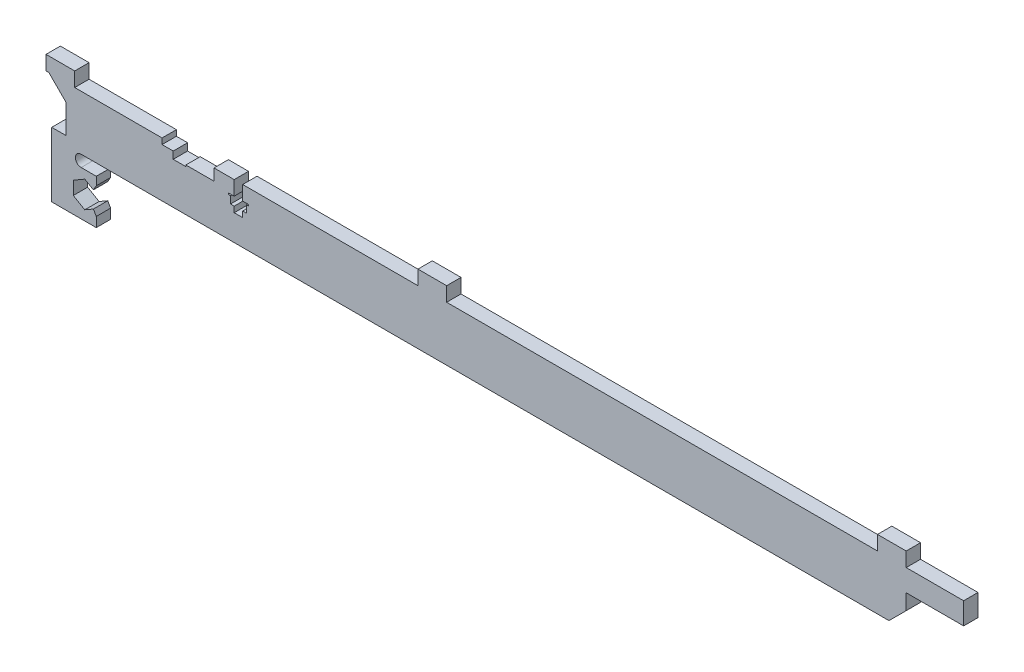
SolidWorks part; units mm, degrees
material "6061-T6 Black anodised"
ref_plane "Front Plane" through (0, 0, 0) normal (0, 0, 1) x (1, 0, 0)
ref_plane "Top Plane" through (0, 0, 0) normal (0, 1, 0) x (1, 0, 0)
ref_plane "Right Plane" through (0, 0, 0) normal (1, 0, 0) x (0, 0, -1)
sketch "Sketch1" plane through (0, 0, 0) normal (0, 0, 1) x (1, 0, 0)
  line L0 (-250.8, 3.6) -> (-241, 3.6)
  line L1 (0, 0) -> (20, 0)
  line L2 (-232.5, 8.6) -> (-232.5, -2.4) construction
  line L3 (0, 7.6) -> (20, 7.6)
  line L4 (20, 0) -> (20, 7.6)
  line L5 (-10, 7.6) -> (-160, 7.6)
  line L6 (0, 0) -> (0, -11.4)
  line L7 (0, -11.4) -> (-287.2708, -11.4)
  line L8 (-292.5, 1.6) -> (-292.5, -8.4)
  line L9 (-259.0932, 7.6) -> (-289.5, 7.6)
  line L10 (-299.5, 7.6) -> (-299.5, 12.6)
  line L11 (-299.5, 12.6) -> (-289.5, 12.6)
  line L12 (-289.5, 7.6) -> (-289.5, 12.6)
  line L13 (-170, 7.6) -> (-170, 12.6)
  line L14 (-250.8, 3.6) -> (-250.8, 3.1)
  line L15 (-250.8, 3.1) -> (-255.2, 3.1)
  line L16 (-255.2, 3.1) -> (-255.2, 5.6)
  line L17 (-255.2, 5.6) -> (-259.0932, 5.6)
  line L18 (0, 7.6) -> (0, 12.6)
  line L19 (0, 12.6) -> (-10, 12.6)
  line L20 (-10, 7.6) -> (-10, 12.6)
  line L21 (-259.0932, 5.6) -> (-259.0932, 7.6)
  line L22 (-255, 3.6) -> (-251, 3.6) construction
  line L23 (-255, 3.6) -> (-255, 13.6) construction
  line L24 (-251, 3.6) -> (-251, 13.6) construction
  line L25 (-255, 13.6) -> (-251, 13.6) construction
  line L26 (-255, 3.6) -> (-251, 13.6) construction
  line L27 (-271, 32.6) -> (-219.2068, 32.6) construction
  line L28 (-271, 32.6) -> (-271, 13.6) construction
  line L29 (-250, 33.6) -> (-250, 13.6) construction
  line L30 (-271, 13.6) -> (-250, 13.6) construction
  line L31 (-271, 32.6) -> (-250, 13.6) construction
  line L32 (-250, 33.6) -> (-271, 13.6) construction
  line L33 (-170, 12.6) -> (-160, 12.6)
  line L34 (-160, 12.6) -> (-160, 7.6)
  line L35 (-170, 7.6) -> (-231.02, 7.6)
  line L36 (-299.5, 7.6) -> (-298.5, 7.6)
  line L37 (-298.5, 7.6) -> (-292.5, 1.6)
  line L38 (-233.98, 7.6) -> (-233.98, 2.6)
  line L39 (-233.98, 2.6) -> (-236, 2.6)
  line L40 (-236, 2.6) -> (-236, 2.1)
  line L41 (-236, 2.1) -> (-235.25, 2.1)
  line L42 (-235.25, 2.1) -> (-235.25, -0.4)
  line L43 (-235.25, -0.4) -> (-233.98, -0.4)
  line L44 (-233.98, -0.4) -> (-233.98, -2.4)
  line L45 (-233.98, -2.4) -> (-231.02, -2.4)
  line L46 (-233.98, 7.6) -> (-241, 7.6)
  line L47 (-231.02, -0.4) -> (-231.02, -2.4)
  line L48 (-229.75, -0.4) -> (-231.02, -0.4)
  line L49 (-229.75, 2.1) -> (-229.75, -0.4)
  line L50 (-229, 2.1) -> (-229.75, 2.1)
  line L51 (-229, 2.6) -> (-229, 2.1)
  line L52 (-231.02, 2.6) -> (-229, 2.6)
  line L53 (-231.02, 7.6) -> (-231.02, 2.6)
  line L54 (-283, -20.0132) -> (-282, -18.2812)
  line L56 (-282, -15.4) -> (-287.2708, -15.4)
  line L57 (-251, 3.6) -> (-255, 13.6) construction
  line L58 (-282, -15.4) -> (-282, -18.2812)
  line L60 (-282, -30.9) -> (-297.5, -30.9)
  line L61 (-297.5, -30.9) -> (-297.5, -8.4)
  line L62 (-297.5, -8.4) -> (-292.5, -8.4)
  line L63 (-283, -25.7868) -> (-282, -27.5188)
  line L64 (-282, -23.9) -> (-282, -20.3633) construction
  line L65 (-283, -20.0132) -> (-286, -18.2812)
  line L66 (-286, -18.2812) -> (-290, -20.5906)
  line L67 (-290, -20.5906) -> (-290, -25.2094)
  line L68 (-290, -25.2094) -> (-286, -27.5188)
  line L69 (-286, -27.5188) -> (-283, -25.7868)
  line L70 (-282, -27.5188) -> (-282, -30.9)
  line L100 (-253, 8.6) -> (-238.8671, 8.6) construction
  line L116 (-241, 7.6) -> (-241, 3.6)
  arc A0 (-287.2708, -11.4) -> (-287.2708, -15.4) centre (-287.2708, -13.4) ccw
  circle A1 centre (-286, -22.9) radius 4 construction
  point P27 (-253, 8.6)
  point P130 (-242, 8.6)
  dimension "D21" = 0.5
  dimension "D24" = 0.5
  dimension "D26" = 2
  dimension "D34" = 8
  dimension "D35" = 2
  dimension "D2" = 20
  dimension "D3" = 7.6
  dimension "D4" = 5
  dimension "D5" = 11.4
  dimension "D6" = 1
  dimension "D7" = 10
  dimension "D8" = 6
  dimension "D9" = 6
  dimension "D10" = 6
  dimension "D11" = 4
  dimension "D12" = 9
  dimension "D13" = 190
  dimension "D14" = 10
  dimension "D15" = 4
  dimension "D16" = 1
  dimension "D17" = 8.5
  dimension "D18" = 20
  dimension "D19" = 42.5
  dimension "D20" = 25
  dimension "D22" = 0.2
  dimension "D23" = 0.2
  dimension "D25" = 2.5
  dimension "D27" = 2.96
  dimension "D28" = 11
  dimension "D29" = 7
  dimension "D30" = 5.5
  dimension "D31" = 270
  dimension "D32" = 11.5
  dimension "D33" = 6.5
  dimension "D36" = 5
  dimension "D37" = 8
  dimension "D38" = 16
  dimension "D45" = 1
extrude "Boss-Extrude1" add sketch "Sketch1" along normal blind 5
chamfer "Chamfer1" distance 6 angle 45 1 edges at (0, -11.4, 2.5)
chamfer "Chamfer2" [suppressed] distance 2.6 angle 60
sketch "Sketch2" plane through (-241, 0, 0) normal (-1, 0, 0) x (0, 0, 1)
  line L0 (5, 5.6) -> (2, 5.6) construction
  line L1 (5, 7.6) -> (5, 3.6) construction
  line L2 (2, 6.475) -> (2, 5.6) construction
  circle A0 centre (2, 5.6) radius 0.4645
extrude "Cut-Extrude1" [suppressed] cut sketch "Sketch2" against normal blind 0.5
equation "\"y-plate-thickness\"=5"
equation "\"bed-plate-thickness\"=3"
equation "\"x-plate-thickness\"=5"
equation "\"rod-diameter\"=12"
equation "\"D4@Sketch1\"=\"x-plate-thickness\""
equation "\"D1@Boss-Extrude1\"=\"x-plate-thickness\""
